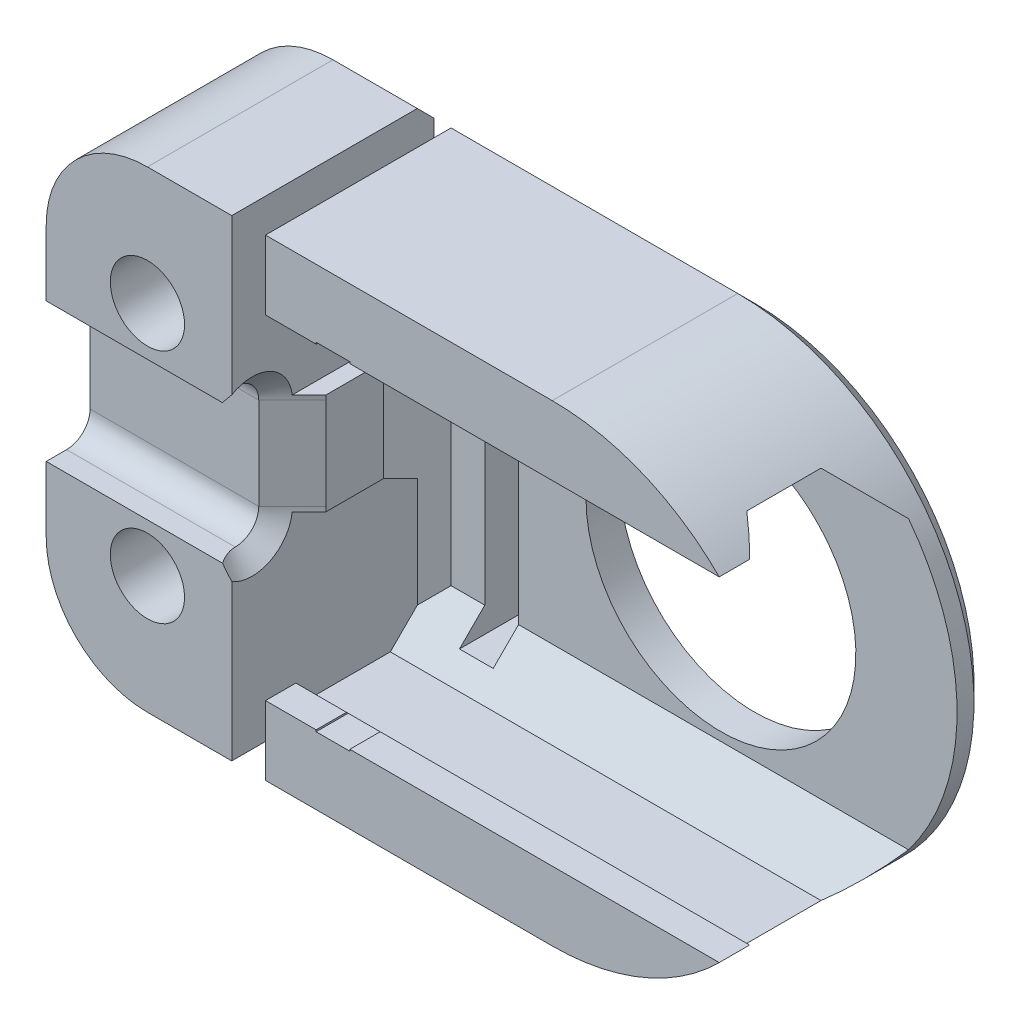
SolidWorks part; units mm, degrees
ref_plane "Front Plane" through (0, 0, 0) normal (0, 0, 1) x (1, 0, 0)
ref_plane "Top Plane" through (0, 0, 0) normal (0, 1, 0) x (1, 0, 0)
ref_plane "Right Plane" through (0, 0, 0) normal (1, 0, 0) x (0, 0, -1)
sketch "Sketch1" plane through (0, 0, 0) normal (0, 0, 1) x (1, 0, 0)
  line L0 (-1.7511, 0) -> (-50001.7511, 0) construction
  line L2 (-15, 7) -> (0, 7)
  line L3 (-15, 7) -> (-15, -7)
  line L4 (-15, -7) -> (0, -7)
  arc A1 (0, 7) -> (0, -7) centre (0, 0) cw
  circle A2 centre (-12, 3.5) radius 1.1
  circle A3 centre (-12, -3.5) radius 1.1
  dimension "D1" = 2.2
  dimension "D2" = 12
  dimension "D3" = 3
  dimension "D4" = 7
  dimension "D5" = 7
extrude "Boss-Extrude1" add sketch "Sketch1" along normal blind 6
sketch "Sketch2" plane through (0, 0, 0) normal (0, 0, -1) x (-1, 0, 0)
  circle A0 centre (0, 0) radius 4
  dimension "D1" = 8
extrude "Cut-Extrude2" cut sketch "Sketch2" against normal blind 10
sketch "Sketch7" plane through (-15, 0, 0) normal (-1, 0, 0) x (0, 0, 1)
  line L0 (2.3, 5.55) -> (1, 4.25)
  line L2 (2.3, 5.55) -> (4.5, 5.55)
  line L3 (4.5, 5.55) -> (5.1, 4.95)
  line L4 (5.1, 4.95) -> (6, 4.95)
  line L5 (6, 7) -> (6, -7) construction
  line L6 (0, 0) -> (8.4762, 0) construction
  line L7 (2.3, 0) -> (6, 0)
  line L8 (6, -4.95) -> (6, 4.95)
  line L9 (5.1, -4.95) -> (6, -4.95)
  line L10 (4.5, -5.55) -> (5.1, -4.95)
  line L11 (2.3, -5.55) -> (4.5, -5.55)
  line L12 (1, 4.25) -> (1, -4.25)
  line L13 (1, -4.25) -> (2.3, -5.55)
  line L14 (0, 7) -> (0, -7) construction
  point P10 (5.55, 4.95)
  dimension "D1" = 45
  dimension "D2" = 2.2
  dimension "D3" = 0.6
  dimension "D4" = 1.5
  dimension "D5" = 11.1
  dimension "D6" = 45
  dimension "D7" = 45
  dimension "D8" = 1
extrude "Cut-Extrude4" cut sketch "Sketch7" against normal through all from offset 6 offset against normal yes
sketch "Sketch8" plane through (-15, 0, 0) normal (-1, 0, 0) x (0, 0, 1)
  line L0 (6, 7) -> (6, -7) construction
  line L1 (4.7, 1.3633) -> (4.7, -1.3633)
  line L2 (6, 2.06) -> (6, -2.06)
  line L3 (0, 0) -> (7.1519, 0) construction
  line L4 (6, 2.06) -> (5.3967, 2.06)
  line L5 (6, -2.06) -> (5.3967, -2.06)
  arc A0 (5.3967, 2.06) -> (4.7, 1.3633) centre (5.3967, 1.3633) ccw
  arc A1 (5.3967, -2.06) -> (4.7, -1.3633) centre (5.3967, -1.3633) cw
  point P8 (4.7, 0)
  point P18 (6, 0)
  dimension "D1" = 4.12
  dimension "D2" = 1.3
extrude "Cut-Extrude6" cut sketch "Sketch8" against normal through all
sketch "Croquis1" plane through (0, 0, 0) normal (0, 0, -1) x (-1, 0, 0)
  line L0 (0, 0) -> (50000, 0) construction
  line L1 (9.5, 7) -> (9.5, 1.5)
  line L2 (0, 7) -> (15, 7) construction
  line L3 (9.5, 1.5) -> (8.5, 1.5)
  line L4 (8.5, 1.5) -> (8.5, 7)
  line L5 (8.5, 7) -> (9.5, 7)
  line L6 (15, 7) -> (15, -7) construction
  line L7 (6, -5) -> (7, -5)
  line L8 (6, -5) -> (6, 5)
  line L9 (6, 5) -> (7, 5)
  line L10 (7, -5) -> (7, 5)
  line L11 (6, -5) -> (7, 5) construction
  line L12 (6, 5) -> (7, -5) construction
  line L13 (8.5, -7) -> (9.5, -7)
  line L14 (8.5, -1.5) -> (8.5, -7)
  line L15 (9.5, -1.5) -> (8.5, -1.5)
  line L16 (9.5, -7) -> (9.5, -1.5)
  point P7 (6.5, 0)
  point P16 (6.5, 5)
  dimension "D1" = 1
  dimension "D2" = 5.5
  dimension "D3" = 1.5
  dimension "D4" = 1
  dimension "D5" = 2
  dimension "D6" = 3
extrude "Cortar-Extruir1" cut sketch "Croquis1" against normal through all
fillet "Fillet4" radius 3 2 edges at (-15, 7, 3) (-15, -7, 3)
fillet "Fillet1" radius 0.5 8 edges at (-14.1213, 6.1213, 0) (-10.75, 7, 0) (-4.25, 7, 0) (7, 0, 0) (-4.25, -7, 0) (-10.75, -7, 0) (-14.1213, -6.1213, 0) (-15, 0, 0) profile chamfer
sketch "Sketch5" plane through (0, 0, 0) normal (0, 0, 1) x (1, 0, 0)
  circle A0 centre (-12, 3.5) radius 1.75
  circle A1 centre (-12, -3.5) radius 1.75
  dimension "D1" = 3.5
extrude "Cut-Extrude5" cut sketch "Sketch5" along normal blind 4
chamfer "Chaflán1" distance 1 angle 45 4 edges at (-9, 0, 4.7) (-9, 0, 1) (-9, 1.432, 4.7034) (-9, -1.432, 4.7034)
